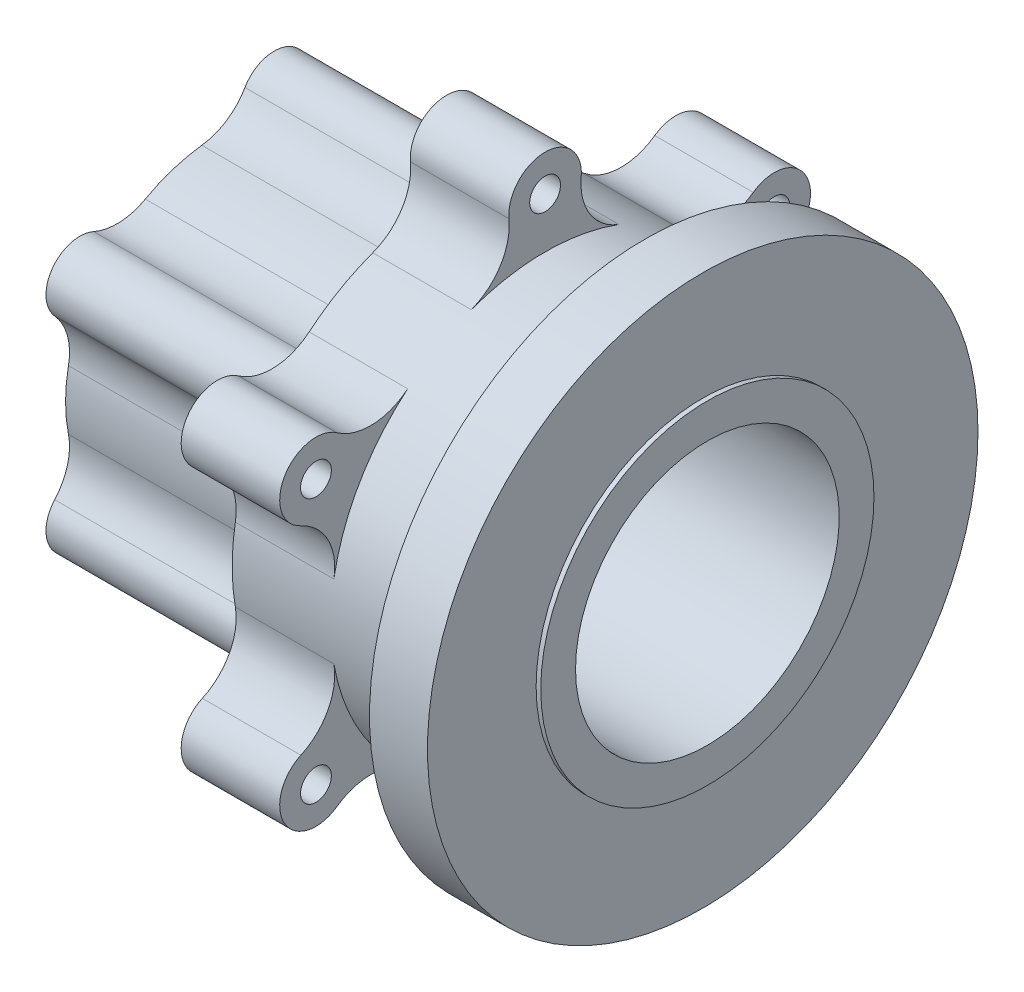
SolidWorks part; units mm, degrees
ref_plane "Front Plane" through (0, 0, 0) normal (1, 0, 0) x (0, 1, 0)
ref_plane "Top Plane" through (0, 0, 0) normal (0, 0, 1) x (0, 1, 0)
ref_plane "Right Plane" through (0, 0, 0) normal (0, 1, 0) x (-1, 0, 0)
sketch "Sketch1" plane through (0, 0, 0) normal (0, 1, 0) x (-1, 0, 0)
  line L0 (0, 68.99) -> (6.35, 68.99)
  line L1 (0, 0) -> (71.12, 0)
  line L2 (0, 0) -> (0, 157.48)
  line L3 (0, 157.48) -> (71.12, 157.48) construction
  line L4 (71.12, 0) -> (71.12, 157.48)
  line L5 (6.35, 68.99) -> (6.35, 149.987)
  line L6 (6.35, 149.987) -> (13.843, 157.48)
  line L7 (63.627, 157.48) -> (71.12, 149.987)
  line L8 (-21.844, 60.325) -> (-21.844, 36.5125)
  line L9 (0, 0) -> (-20.32, 0)
  line L10 (0, 0) -> (0, 46.99)
  line L11 (0, 46.99) -> (-20.32, 46.99)
  line L12 (-20.32, 0) -> (-20.32, 46.99)
  line L13 (71.12, 0) -> (83.82, 0) construction
  line L14 (71.12, 0) -> (71.12, 14.9987) construction
  line L15 (71.12, 14.9987) -> (83.82, 14.9987) construction
  line L16 (83.82, 0) -> (83.82, 14.9987) construction
  line L17 (83.82, 0) -> (96.52, 0) construction
  line L18 (83.82, 0) -> (83.82, 24.13) construction
  line L19 (83.82, 24.13) -> (96.52, 24.13) construction
  line L20 (96.52, 0) -> (96.52, 24.13) construction
  line L21 (-20.32, 0) -> (-35.56, 0)
  line L22 (-20.32, 0) -> (-20.32, 36.5125)
  line L23 (-20.32, 36.5125) -> (-35.56, 36.5125)
  line L24 (-35.56, 0) -> (-35.56, 36.5125)
  line L25 (-21.844, 36.5125) -> (-34.544, 36.5125)
  line L26 (-34.544, 36.5125) -> (-34.544, 60.325)
  line L27 (-34.544, 60.325) -> (-21.844, 60.325)
  line L28 (6.35, 68.99) -> (71.12, 68.99)
  dimension "D1" = 157.48
  dimension "D2" = 71.12
  dimension "D3" = 12.7
  dimension "D4" = 12.7
  dimension "D5" = 14.9987
  dimension "D6" = 24.13
  dimension "D7" = 20.32
  dimension "D8" = 45
  dimension "D9" = 45
  dimension "D10" = 6.35
  dimension "D11" = 46.99
  dimension "D13" = 36.5125
  dimension "D14" = 132.08
  dimension "D12" = 49.784
  dimension "D16" = 60.325
  dimension "D17" = 12.7
  dimension "D18" = 36.5125
  dimension "D19" = 68.99
  dimension "D15" = 1.016
revolve "Revolve1" add sketch "Sketch1" angle 360 about L1 region at (-35.56, 0, 34.495) region at (10.16, 0, 23.495) region at (27.94, 0, 18.2562)
revolve "Revolve2" add sketch "Sketch1<3>" angle 360 about L1 region at (28.194, 0, 48.4187)
sketch "Sketch1<3>" plane through (0, 0, 0) normal (0, 1, 0) x (-1, 0, 0) same geometry as "Sketch1"
sketch "Sketch2" plane through (-71.12, 0, 0) normal (-1, 0, 0) x (0, -1, 0)
  line L1 (0, -38.1) -> (36.2353, -11.7735)
  line L2 (36.2353, -11.7735) -> (22.3946, 30.8235)
  line L3 (22.3946, 30.8235) -> (-22.3946, 30.8235)
  line L4 (-22.3946, 30.8235) -> (-36.2353, -11.7735)
  line L5 (-36.2353, -11.7735) -> (0, -38.1)
  circle A0 centre (0, 0) radius 38.1
  circle A1 centre (0, 0) radius 68.99
  circle A3 centre (0, 0) radius 30.8235 construction
  circle A5 centre (0, 0) radius 68.99
  dimension "D2" = 76.2
  dimension "D1" = 0
sketch "Sketch3" plane through (-71.12, 0, 0) normal (-1, 0, 0) x (0, -1, 0)
  circle A0 centre (-22.3946, 30.8235) radius 3.3734
  circle A1 centre (22.3946, 30.8235) radius 3.3734
  circle A2 centre (36.2353, -11.7735) radius 3.3734
  circle A3 centre (0, -38.1) radius 3.3734
  circle A4 centre (-36.2353, -11.7735) radius 3.3734
  point P0 (-36.2353, -11.7735)
  point P2 (0, -38.1)
  point P4 (36.2353, -11.7735)
  point P6 (22.3946, 30.8235)
  point P8 (-22.3946, 30.8235)
  dimension "D1" = 6.7469
extrude "Cut-Extrude1" cut sketch "Sketch3" against normal blind 13.97
sketch "Sketch4" plane through (0, 0, 0) normal (1, 0, 0) x (0, 1, 0)
  line L0 (28.995, -50.2208) -> (57.99, 0)
  line L1 (57.99, 0) -> (28.995, 50.2208)
  line L2 (28.995, 50.2208) -> (-28.995, 50.2208)
  line L3 (-28.995, 50.2208) -> (-57.99, 0)
  line L4 (-57.99, 0) -> (-28.995, -50.2208)
  line L5 (-28.995, -50.2208) -> (28.995, -50.2208)
  circle A0 centre (0, 0) radius 50.2208 construction
  circle A1 centre (0, 0) radius 68.99
  circle A2 centre (0, 0) radius 68.99
  circle A3 centre (28.995, 50.2208) radius 3.3734
  dimension "D3" = 6.7469
  dimension "D2" = 115.98
  dimension "D1" = 0
sketch "Sketch5" plane through (0, 0, 0) normal (1, 0, 0) x (0, 1, 0)
  circle A0 centre (28.995, 50.2208) radius 3.3734 construction
  circle A1 centre (28.995, 50.2208) radius 3.3734
  circle A2 centre (-28.995, 50.2208) radius 3.3734
  circle A3 centre (-57.99, 0) radius 3.3734
  circle A4 centre (-28.995, -50.2208) radius 3.3734
  circle A5 centre (28.995, -50.2208) radius 3.3734
  circle A6 centre (57.99, 0) radius 3.3734
  point P0 (28.995, -50.2208)
  point P2 (57.99, 0)
  point P4 (28.995, 50.2208)
  point P9 (-28.995, -50.2208)
  point P11 (-57.99, 0)
  point P13 (-28.995, 50.2208)
extrude "Cut-Extrude2" cut sketch "Sketch5" against normal blind 13.97
sketch "Sketch10" plane through (0, 0, 0) normal (1, 0, 0) x (0, 1, 0)
  line L0 (-28.995, 50.2208) -> (0, 0) construction
  circle A0 centre (0, -38.1) radius 3.3734 construction
  circle A1 centre (-36.2353, -11.7735) radius 3.3734 construction
  circle A2 centre (-22.3946, 30.8235) radius 3.3734 construction
  circle A3 centre (36.2353, -11.7735) radius 3.3734 construction
  circle A4 centre (22.3946, 30.8235) radius 3.3734 construction
  circle A5 centre (0, -38.1) radius 3.3734
  circle A6 centre (-36.2353, -11.7735) radius 3.3734
  circle A7 centre (-22.3946, 30.8235) radius 3.3734
  circle A8 centre (36.2353, -11.7735) radius 3.3734
  circle A9 centre (22.3946, 30.8235) radius 3.3734
  circle A10 centre (57.99, 0) radius 3.3734 construction
  circle A11 centre (28.995, -50.2208) radius 3.3734 construction
  circle A12 centre (-28.995, -50.2208) radius 3.3734 construction
  circle A13 centre (-57.99, 0) radius 3.3734 construction
  circle A14 centre (-28.995, 50.2208) radius 3.3734 construction
  circle A15 centre (28.995, 50.2208) radius 3.3734 construction
  circle A16 centre (57.99, 0) radius 3.3734
  circle A17 centre (28.995, -50.2208) radius 3.3734
  circle A18 centre (-28.995, -50.2208) radius 3.3734
  circle A19 centre (-57.99, 0) radius 3.3734
  circle A20 centre (-28.995, 50.2208) radius 3.3734
  circle A21 centre (28.995, 50.2208) radius 3.3734
  circle A22 centre (0, 0) radius 68.99 construction
  circle A23 centre (0, 0) radius 46.99 construction
  circle A24 centre (0, 0) radius 68.99
  circle A25 centre (0, 0) radius 46.99
  circle A26 centre (-28.995, 50.2208) radius 7.9454
  arc A27 (-35.4699, 45.6159) -> (-36.0706, 30.1159) centre (-45.8195, 38.2554) cw
  arc A28 (-21.7696, 53.5258) -> (-8.0458, 46.2961) centre (-10.2204, 58.8085) ccw
  arc A29 (35.4699, 45.6159) -> (36.0706, 30.1159) centre (45.8195, 38.2554) ccw
  circle A30 centre (28.995, 50.2208) radius 7.9454
  arc A31 (21.7696, 53.5258) -> (8.0458, 46.2961) centre (10.2204, 58.8085) cw
  arc A32 (57.2395, -7.9099) -> (44.1165, -16.1801) centre (56.0399, -20.5531) ccw
  circle A33 centre (57.99, 0) radius 7.9454
  arc A34 (57.2395, 7.9099) -> (44.1165, 16.1801) centre (56.0399, 20.5531) cw
  arc A35 (21.7696, -53.5258) -> (8.0458, -46.2961) centre (10.2204, -58.8085) ccw
  circle A36 centre (28.995, -50.2208) radius 7.9454
  arc A37 (35.4699, -45.6159) -> (36.0706, -30.1159) centre (45.8195, -38.2554) cw
  arc A38 (-35.4699, -45.6159) -> (-36.0706, -30.1159) centre (-45.8195, -38.2554) ccw
  circle A39 centre (-28.995, -50.2208) radius 7.9454
  arc A40 (-21.7696, -53.5258) -> (-8.0458, -46.2961) centre (-10.2204, -58.8085) cw
  arc A41 (-57.2395, 7.9099) -> (-44.1165, 16.1801) centre (-56.0399, 20.5531) ccw
  circle A42 centre (-57.99, 0) radius 7.9454
  arc A43 (-57.2395, -7.9099) -> (-44.1165, -16.1801) centre (-56.0399, -20.5531) cw
  point P45 (40.0761, 36.1136)
  point P46 (0, 0)
  point P87 (0, 0)
  circle M12 centre (0, 0) radius 68.99
  circle M13 centre (0, 0) radius 46.99
  dimension "D1" = 4.572
  dimension "D2" = 12.7
  dimension "D3" = 6
extrude "Cut-Extrude3" cut sketch "Sketch10" against normal through all contours A43 A42 A41 A27 A26 A28 A25 A31 A30 A29 A34 A33 A32 A37 A36 A35 A40 A39 A38 M12 M13 region at (0, -67.0387, 0)
ref_plane "Plane1" through (-21.59, 0, 0) normal (1, 0, 0) x (0, 0, -1)
sketch "Sketch12" plane through (-21.59, 0, 0) normal (1, 0, 0) x (0, 0, -1)
  circle A0 centre (0, 0) radius 46.99 construction
  circle A1 centre (0, 0) radius 46.99
  circle A2 centre (0, 0) radius 65.9354
  arc A3 (-7.9099, -57.2395) -> (7.9099, -57.2395) centre (0, -57.99) ccw construction
extrude "Cut-Extrude6" cut sketch "Sketch12" against normal through all
sketch "Sketch13" plane through (-71.12, 0, 0) normal (-1, 0, 0) x (0, -1, 0)
  line L0 (0, 0) -> (0, 28.8925) construction
  circle A0 centre (0, 0) radius 36.5125 construction
  circle A1 centre (0, 0) radius 36.5125 construction
  circle A2 centre (0, 0) radius 46.99 construction
  circle A3 centre (22.3946, 30.8235) radius 3.3734 construction
  circle A4 centre (-22.3946, 30.8235) radius 3.3734 construction
  circle A5 centre (0, 0) radius 46.99
  circle A6 centre (22.3946, 30.8235) radius 3.3734
  circle A7 centre (-22.3946, 30.8235) radius 3.3734
  circle A8 centre (0, 0) radius 28.8925
  circle A9 centre (0, 0) radius 33.9725
  circle A10 centre (-22.3946, 30.8235) radius 7.4374
  arc A11 (-17.426, 36.3578) -> (-6.5085, 33.3432) centre (-8.9416, 45.808) ccw
  circle A12 centre (22.3946, 30.8235) radius 7.4374
  arc A13 (17.426, 36.3578) -> (6.5085, 33.3432) centre (8.9416, 45.808) cw
  arc A14 (39.9632, -5.3379) -> (33.7225, 4.1137) centre (46.3291, 5.6515) cw
  arc A15 (29.1934, 27.8083) -> (29.7, 16.4936) centre (40.8029, 22.6594) ccw
  circle A16 centre (36.2353, -11.7735) radius 7.4374
  arc A17 (7.2727, -39.6568) -> (14.3331, -30.8008) centre (19.6913, -42.3152) cw
  arc A18 (35.4685, -19.1714) -> (24.8642, -23.1496) centre (34.1592, -31.8037) ccw
  circle A19 centre (0, -38.1) radius 7.4374
  arc A20 (-35.4685, -19.1714) -> (-24.8642, -23.1496) centre (-34.1592, -31.8037) cw
  arc A21 (-7.2727, -39.6568) -> (-14.3331, -30.8008) centre (-19.6913, -42.3152) ccw
  circle A22 centre (-36.2353, -11.7735) radius 7.4374
  arc A23 (-29.1934, 27.8083) -> (-29.7, 16.4936) centre (-40.8029, 22.6594) cw
  arc A24 (-39.9632, -5.3379) -> (-33.7225, 4.1137) centre (-46.3291, 5.6515) ccw
  circle A25 centre (-22.3946, 30.8235) radius 7.4374
  point P22 (0, 0)
  point P23 (23.8513, -33.6169)
  point P24 (0, 0)
  point P57 (0, 0)
  circle M8 centre (0, 0) radius 46.99
  dimension "D1" = 7.62
  dimension "D2" = 5.08
  dimension "D3" = 4.064
  dimension "D4" = 12.7
  dimension "D5" = 5
extrude "Cut-Extrude7" cut sketch "Sketch13" against normal up to surface (49.53 mm away) contours A22 A24 A9 A23 A10 A11 A13 A12 A15 A14 A16 A18 A17 A19 A21 A20 M8 region at (-71.12, 45.6609, 0) up to face at (-21.59, 26.4329, 45.783)
extrude "Cut-Extrude8" cut sketch "Sketch13<3>" against normal through all contours A8 region at (-71.12, 0, 0)
sketch "Sketch13<3>" plane through (-71.12, 0, 0) normal (-1, 0, 0) x (0, -1, 0) same geometry as "Sketch13"
equation "\"D9@Sketch1\"=\"D8@Sketch1\""
equation "\"D19@Sketch1\"=115.98mm-\"D11@Sketch1\""
